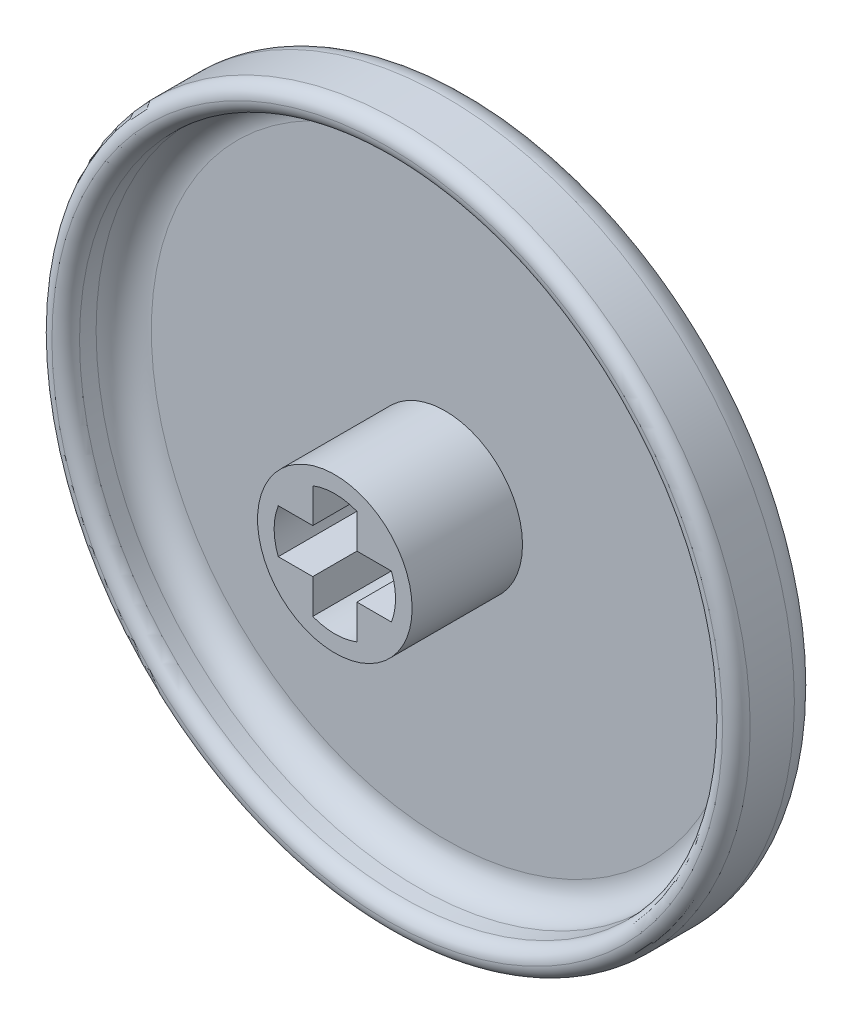
SolidWorks part; units mm, degrees
ref_plane "前视基准面" through (0, 0, 0) normal (0, 0, 1) x (1, 0, 0)
ref_plane "上视基准面" through (0, 0, 0) normal (0, 1, 0) x (1, 0, 0)
ref_plane "右视基准面" through (0, 0, 0) normal (1, 0, 0) x (0, 0, -1)
other "Configuration Table"
sketch "草图1" plane through (0, 0, 0) normal (0, 0, 1) x (1, 0, 0)
  line L0 (-0.8, 0) -> (0.8, 0) construction
  line L1 (0, -0.8) -> (0, 0.8) construction
  line L5 (-0.8, -2.0494) -> (-0.8, -0.8)
  line L8 (0.8, -2.0494) -> (0.8, -0.8)
  line L11 (-2.0494, 0.8) -> (-0.8, 0.8)
  line L14 (-2.0494, -0.8) -> (-0.8, -0.8)
  line L17 (-0.8, 0.8) -> (-0.8, 2.0494)
  line L18 (0.8, 0.8) -> (2.0494, 0.8)
  line L19 (0.8, 0.8) -> (0.8, 2.0494)
  line L20 (0.8, -0.8) -> (2.0494, -0.8)
  circle A1 centre (0, 0) radius 2.8
  circle A3 centre (0, 0) radius 12.65
  circle A5 centre (0, 0) radius 11.65
  circle A6 centre (0, 0) radius 2.2
  point P4 (0, 0)
  point P5 (0, 0)
  point P6 (0, 0)
  point P8 (0, 0)
  point P9 (0, 0)
  point P11 (0, 0)
  point P14 (-0.8, 0)
  point P19 (0.8, 0)
  point P21 (0, 0.8)
  point P22 (0, 0)
  point P30 (0, -0.8)
  dimension "D1" = 5.6
  dimension "D7" = 25.3
  dimension "D2" = 4.4
  dimension "D3" = 1.6
  dimension "D4" = 1.6
extrude "凸台-拉伸1" add sketch "草图1" along normal blind 4 contours L14 A6 L5 | L17 A6 L11 | L18 A6 L19 | L8 A6 L20 | A1 A6 region at (-1.2738, -1.2738, 0) region at (1.2738, -1.2738, 0) region at (-1.2738, 1.2738, 0) region at (1.2738, 1.2738, 0) region at (-2.7208, 0, 0)
extrude "凸台-拉伸2" add sketch "草图1<12>" against normal blind 1 contours L17 A6 L11 | L14 A6 L5 | L19 A6 L17 L11 L14 L5 L8 L20 L18 | L8 A6 L20 | L18 A6 L19 | A1 A6 | A5 A1 region at (-1.2738, -1.2738, 0) region at (0, 0, 0) region at (1.2738, -1.2738, 0) region at (-1.2738, 1.2738, 0) region at (1.2738, 1.2738, 0) region at (-2.7208, 0, 0) region at (-11.3205, 0, 0)
sketch "草图1<12>" plane through (0, 0, 0) normal (0, 0, 1) x (1, 0, 0) same geometry as "草图1"
extrude "凸台-拉伸3" add sketch "草图1<13>" along normal blind 2.1 and the other way blind 1 contours A3 A5 region at (-12.2922, 0, 0)
sketch "草图1<13>" plane through (0, 0, 0) normal (0, 0, 1) x (1, 0, 0) same geometry as "草图1"
fillet "圆角1" radius 1 2 edges at (11.65, 0, 0) (12.65, 0, -1)
fillet "圆角2" radius 0.5 1 edges at (11.65, 0, 2.1) type face fillet first side face at (11.65, 0, 1) second side face at (11.65, 0, 2.1)
fillet "圆角3" radius 0.5 1 edges at (12.65, 0, 2.1) type face fillet first side face at (12.65, 0, 0) second side face at (12.15, 0, 2.1)
